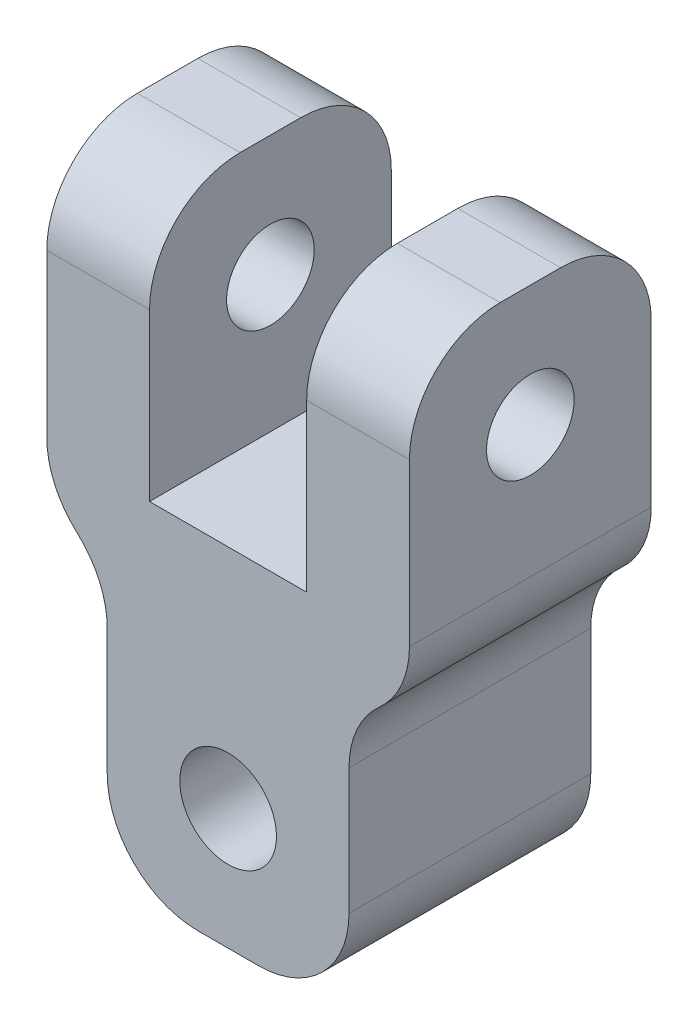
SolidWorks part; units mm, degrees
ref_plane "Front" through (0, 0, 0) normal (0, 0, 1) x (1, 0, 0)
ref_plane "Top" through (0, 0, 0) normal (0, 1, 0) x (1, 0, 0)
ref_plane "Right" through (0, 0, 0) normal (1, 0, 0) x (0, 0, -1)
sketch "草图1" plane through (0, 0, 0) normal (0, 1, 0) x (1, 0, 0)
  line L1 (0, 0) -> (8, 0)
  line L2 (0, 0) -> (0, -8)
  line L3 (0, -8) -> (8, -8)
  line L4 (8, 0) -> (8, -8)
  dimension "D1" = 8
  dimension "D2" = 8
extrude "凸台-拉伸1" add sketch "草图1" along normal blind 20
sketch "草图2" plane through (0, 0, 8) normal (0, 0, 1) x (1, 0, 0)
  line L0 (0, 0) -> (8, 0) construction
  line L1 (8, 20) -> (8, 0) construction
  circle A0 centre (4, 4) radius 1.6
  dimension "D1" = 3.2
  dimension "D2" = 4
  dimension "D3" = 4
extrude "切除-拉伸1" cut sketch "草图2" against normal through all
sketch "草图4" plane through (0, 20, 0) normal (0, 1, 0) x (1, 0, 0)
  line L1 (0, 0) -> (-2, 0)
  line L2 (0, 0) -> (0, -8)
  line L3 (0, -8) -> (-2, -8)
  line L4 (-2, 0) -> (-2, -8)
  line L5 (8, 0) -> (10, 0)
  line L6 (8, 0) -> (8, -8)
  line L7 (8, -8) -> (10, -8)
  line L8 (10, 0) -> (10, -8)
  dimension "D1" = 2
  dimension "D2" = 2
  dimension "D3" = 8
  dimension "D4" = 8
extrude "凸台-拉伸3" add sketch "草图4" against normal blind 10
sketch "草图5" plane through (0, 0, 8) normal (0, 0, 1) x (1, 0, 0)
  line L0 (-2, 20) -> (10, 20) construction
  line L1 (1.4, 20) -> (6.6, 20)
  line L2 (1.4, 20) -> (1.4, 11.5)
  line L3 (1.4, 11.5) -> (6.6, 11.5)
  line L4 (6.6, 20) -> (6.6, 11.5)
  dimension "D1" = 5.2
  dimension "D2" = 3.4
  dimension "D3" = 8.5
extrude "切除-拉伸2" cut sketch "草图5" against normal through all
fillet "圆角1" radius 3 2 edges at (8, 10, 4) (0, 10, 4)
sketch "草图6" plane through (10, 0, 0) normal (1, 0, 0) x (0, 0, -1)
  line L0 (-8, 20) -> (0, 20) construction
  line L1 (0, 10) -> (0, 20) construction
  circle A0 centre (-4, 16) radius 1.45
  dimension "D1" = 2.9
  dimension "D2" = 4
  dimension "D3" = 4
extrude "切除-拉伸3" cut sketch "草图6" against normal through all
fillet "圆角2" radius 3 6 edges at (-2, 10, 4) (10, 10, 4) (-0.3, 20, 0) (-0.3, 20, 8) (0, 0, 4) (8, 0, 4)
